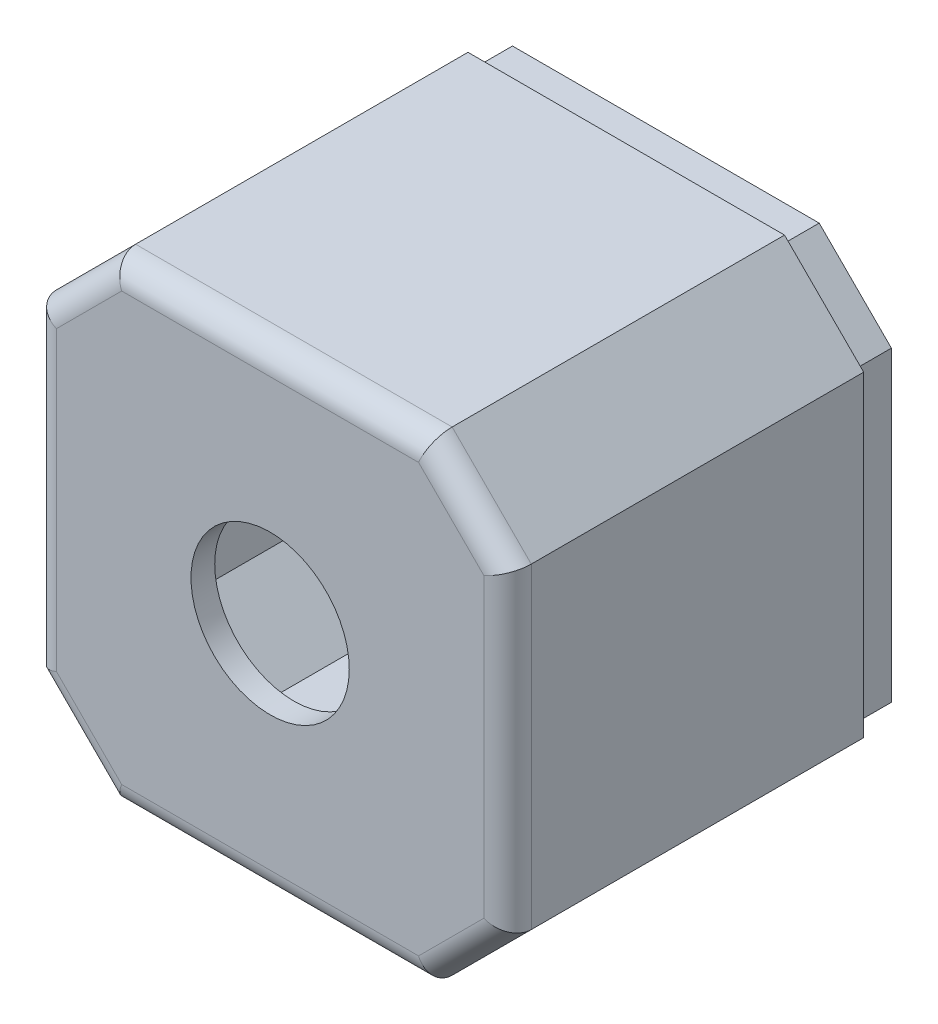
SolidWorks part; units mm, degrees
material "Chrome Stainless Steel"
ref_plane "Front" through (0, 0, 0) normal (0, 0, 1) x (1, 0, 0)
ref_plane "Top" through (0, 0, 0) normal (0, 1, 0) x (1, 0, 0)
ref_plane "Right" through (0, 0, 0) normal (1, 0, 0) x (0, 0, -1)
sketch "Sketch1" plane through (0, 0, 0) normal (0, 0, 1) x (1, 0, 0)
  line L1 (0, 0) -> (60, 0)
  line L2 (0, 0) -> (0, 60)
  line L3 (0, 60) -> (60, 60)
  line L4 (60, 0) -> (60, 60)
  dimension "D1" = 60
  dimension "D2" = 60
extrude "Boss-Extrude1" add sketch "Sketch1" along normal blind 50
chamfer "Chamfer1" distance 10 angle 45 4 edges at (0, 60, 25) (0, 0, 25) (60, 0, 25) (60, 60, 25)
fillet "Fillet1" radius 3 8 edges at (5, 55, 50) (30, 60, 50) (55, 55, 50) (60, 30, 50) (55, 5, 50) (30, 0, 50) (5, 5, 50) (0, 30, 50)
shell "Shell2" thickness 3 removed face at (30, 30, 0)
sketch "Sketch2" plane through (0, 0, 50) normal (0, 0, 1) x (1, 0, 0)
  line L0 (60, 50) -> (60, 10) construction
  line L1 (50, 0) -> (10, 0) construction
  circle A0 centre (30, 30) radius 10
  dimension "D1" = 20
  dimension "D2" = 30
  dimension "D3" = 30
extrude "Cut-Extrude1" cut sketch "Sketch2" against normal up to next
sketch "Sketch3" plane through (0, 0, 0) normal (0, 0, -1) x (-1, 0, 0)
  line L8 (0, 10) -> (0, 50)
  line L9 (0, 50) -> (-10, 60)
  line L10 (-10, 60) -> (-50, 60)
  line L11 (-50, 60) -> (-60, 50)
  line L12 (-60, 50) -> (-60, 10)
  line L13 (-60, 10) -> (-50, 0)
  line L14 (-50, 0) -> (-10, 0)
  line L15 (-10, 0) -> (0, 10)
  line L16 (0, 10) -> (0, 50)
  line L17 (0, 50) -> (-10, 60)
  line L18 (-10, 60) -> (-50, 60)
  line L19 (-50, 60) -> (-60, 50)
  line L20 (-60, 50) -> (-60, 10)
  line L21 (-60, 10) -> (-50, 0)
  line L22 (-50, 0) -> (-10, 0)
  line L23 (-10, 0) -> (0, 10)
  line L32 (-1.5, 10.6213) -> (-1.5, 49.3787)
  line L33 (-1.5, 49.3787) -> (-10.6213, 58.5)
  line L34 (-10.6213, 58.5) -> (-49.3787, 58.5)
  line L35 (-49.3787, 58.5) -> (-58.5, 49.3787)
  line L36 (-58.5, 49.3787) -> (-58.5, 10.6213)
  line L37 (-58.5, 10.6213) -> (-49.3787, 1.5)
  line L38 (-49.3787, 1.5) -> (-10.6213, 1.5)
  line L39 (-10.6213, 1.5) -> (-1.5, 10.6213)
  line L40 (-1.5, 10.6213) -> (-1.5, 49.3787)
  line L41 (-1.5, 49.3787) -> (-10.6213, 58.5)
  line L42 (-10.6213, 58.5) -> (-49.3787, 58.5)
  line L43 (-49.3787, 58.5) -> (-58.5, 49.3787)
  line L44 (-58.5, 49.3787) -> (-58.5, 10.6213)
  line L45 (-58.5, 10.6213) -> (-49.3787, 1.5)
  line L46 (-49.3787, 1.5) -> (-10.6213, 1.5)
  line L47 (-10.6213, 1.5) -> (-1.5, 10.6213)
  dimension "D1" = 0
  dimension "D2" = 1.5
extrude "Cut-Extrude2" cut sketch "Sketch3" against normal blind 5
